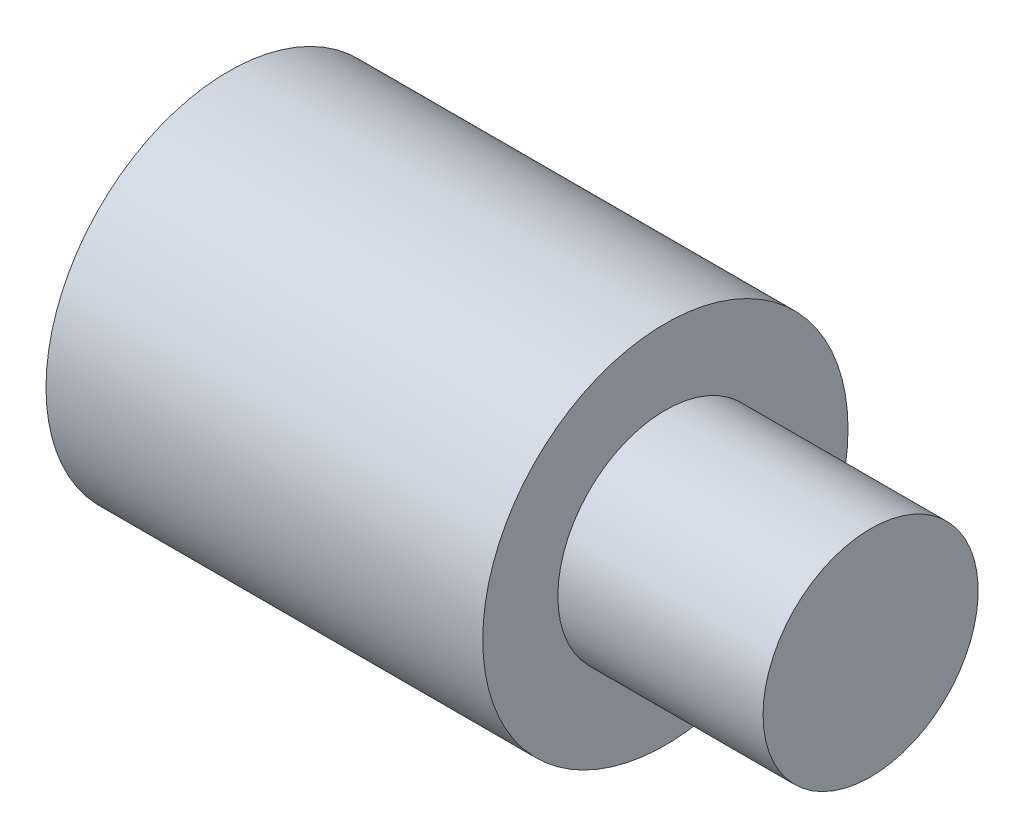
SolidWorks part; units mm, degrees
ref_plane "Front Plane" through (0, 0, 0) normal (0, 0, 1) x (1, 0, 0)
ref_plane "Top Plane" through (0, 0, 0) normal (0, 1, 0) x (1, 0, 0)
ref_plane "Right Plane" through (0, 0, 0) normal (1, 0, 0) x (0, 0, -1)
sketch "Conn_T8_ORB6 Sketch" plane through (0, 0, 0) normal (0, 0, 1) x (1, 0, 0)
  line L0 (-1000, 0) -> (1000, 0) construction
  line L1 (12.5, 0) -> (12.5, 6.55)
  line L2 (12.5, 6.55) -> (0, 6.55)
  line L3 (0, 6.55) -> (0, 11.124)
  line L4 (0, 11.124) -> (-26.6, 11.124)
  line L5 (-26.6, 11.124) -> (-26.6, 0)
  line L6 (-26.6, 0) -> (12.5, 0)
revolve "Conn_T8_ORB6" add sketch "Conn_T8_ORB6 Sketch" angle 360 about L0
ref_axis "Engine Axis" through (14.455, 0, 0) along (-1, 0, 0)
sketch "Socket Sketch" plane through (0, 0, 0) normal (0, 0, 1) x (1, 0, 0)
  line L0 (-1000, 0) -> (1000, 0) construction
  line L1 (-27.6, 0) -> (-27.6, 6.35)
  line L2 (-27.6, 6.35) -> (-3.7, 6.35)
  line L3 (-3.7, 6.35) -> (-3.7, 0)
  line L4 (-3.7, 0) -> (-27.6, 0)
revolve "Socket" cut sketch "Socket Sketch" angle 360 about L0
